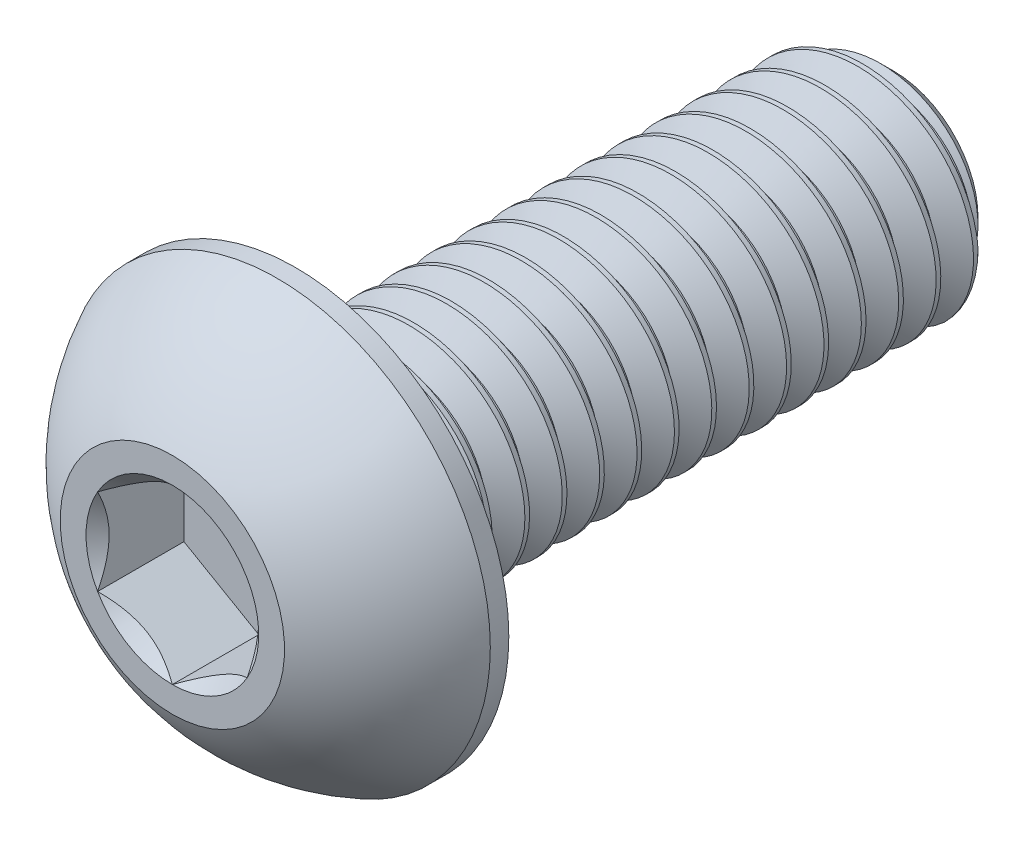
SolidWorks part; units mm, degrees
ref_plane "Front" through (0, 0, 0) normal (0, 0, 1) x (1, 0, 0)
ref_plane "Top" through (0, 0, 0) normal (0, 1, 0) x (1, 0, 0)
ref_plane "Right" through (0, 0, 0) normal (1, 0, 0) x (0, 0, -1)
sketch "Sketch1" plane through (0, 0, 0) normal (1, 0, 0) x (0, 0, -1)
  line L2 (1.65, 1.5) -> (9.65, 1.5)
  line L3 (9.65, 1.5) -> (9.65, 0)
  line L4 (9.65, 0) -> (1.65, 0)
  line L6 (1.4025, 2.85) -> (1.65, 2.85) construction
  line L7 (9.65, 1.5) -> (9.65, -1.5) construction
  line L8 (0, 0) -> (1.65, 0) construction
  line L9 (1.65, 2.85) -> (1.65, -2.85) construction
  line L11 (1.65, 1.5) -> (1.65, 0)
  line L13 (0, 1) -> (0, -1) construction
  line L14 (0, 1) -> (0, 1.5) construction
  arc A3 (0, 1.5) -> (1.4025, 2.85) centre (2.7948, 0) cw construction
  dimension "D1" = 0.2475
  dimension "Head Ht" = 1.65
  dimension "Head Dia" = 5.7
  dimension "Dia" = 3
  dimension "Lg" = 8
  dimension "Hex" = 2
revolve "Revolve1" add sketch "Sketch1" angle 360 mid plane about L4
sketch "Sketch3" plane through (0, 0, -9.65) normal (0, 0, -1) x (-1, 0, 0)
  circle A0 centre (0, 0) radius 1.5
curve "Helix/Spiral1" pitch 0.5 height 8.5 radius 1.5 centre (0, 0, -9.65) axis (0, 0, 1) start towards (0, 1, 0)
sketch "Sketch2" plane through (0, 0, 0) normal (1, 0, 0) x (0, 0, -1)
  line L0 (9.65, 1.5) -> (10.0875, 1.5)
  line L1 (10.0875, 1.5) -> (9.9, 1.1752)
  line L2 (9.9, 1.1752) -> (9.8375, 1.1752)
  line L3 (9.8375, 1.1752) -> (9.65, 1.5)
  line L4 (9.7438, 1.3376) -> (9.9938, 1.3376) construction
  dimension "D1" = 60
  dimension "D2" = 0.0625
  dimension "D3" = 0.25
chamfer "Chamfer1" distance 0.375 angle 45 1 edges at (0, 1.5, -9.65)
sweep "Cut-Sweep1" cut profiles "Sketch2" path "Helix/Spiral1"
sketch "Sketch7" plane through (0, 0, 0) normal (1, 0, 0) x (0, 0, -1)
  line L6 (1.4025, 2.85) -> (1.65, 2.85) construction
  line L8 (0, 0) -> (1.65, 0) construction
  line L11 (1.65, 2.85) -> (1.65, -2.85) construction
  line L12 (1.4025, 2.85) -> (1.65, 2.85)
  line L13 (0, 0) -> (1.65, 0)
  line L14 (0, 1) -> (0, -1) construction
  line L15 (1.65, 2.85) -> (1.65, 0)
  line L16 (0, 1.5) -> (0, 0)
  arc A2 (1.4025, 2.85) -> (0, 1.5) centre (2.7948, 0) ccw construction
  arc A3 (1.4025, 2.85) -> (0, 1.5) centre (2.7948, 0) ccw
revolve "Revolve2" add sketch "Sketch7" angle 360 mid plane about L13
sketch "Sketch5" plane through (0, 0, 0) normal (0, 0, 1) x (1, 0, 0)
  line L1 (1, -0.5774) -> (1, 0.5774)
  line L2 (1, 0.5774) -> (0, 1.1547)
  line L3 (0, 1.1547) -> (-1, 0.5774)
  line L4 (-1, 0.5774) -> (-1, -0.5774)
  line L5 (-1, -0.5774) -> (0, -1.1547)
  line L6 (0, -1.1547) -> (1, -0.5774)
  circle A0 centre (0, 0) radius 1 construction
extrude "Cut-Extrude2" cut sketch "Sketch5" against normal blind 1.155
sketch "Sketch6" plane through (0, 0, 0) normal (0, 0, 1) x (1, 0, 0)
  circle A0 centre (0, 0) radius 1.1547
extrude "Cut-Extrude3" cut sketch "Sketch6" against normal blind 1.155 draft 45
sketch "Sketch9" [suppressed] plane through (0, 0, -6.6) normal (0, 0, 1) x (1, 0, 0)
  circle A2 centre (0, 0) radius 6
extrude "Boss-Extrude2" [suppressed] add sketch "Sketch9" against normal offset from surface (19 mm away) 32 up to face at (0, 1.125, -9.65)
sketch "Sketch10" plane through (0, 0, 0) normal (1, 0, 0) x (0, 0, -1)
  line L0 (9.65, 1.5) -> (9.65, -1.5) construction
  point P0 (8.9, -1.5)
  dimension "D1" = 0.75
equation "\"D3@Helix/Spiral1\" = \"Lg@Sketch1\" + \"D4@Helix/Spiral1\""
equation "\"D2@Sketch2\" = \"D4@Helix/Spiral1\" * .125"
equation "\"D3@Sketch2\" = \"D4@Helix/Spiral1\" * .5"
equation "\"D1@Chamfer1\" = \"D4@Helix/Spiral1\" * .75"
equation "\"D1@Cut-Extrude2\" = \"Head Ht@Sketch1\" * .7"
equation "\"D1@Sketch1\" = \"Head Ht@Sketch1\" * .15"
equation "\"D1@Sketch10\" = \"D4@Helix/Spiral1\" * 1.5"
equation "\"D1@Cut-Extrude3\" = \"D1@Cut-Extrude2\""
